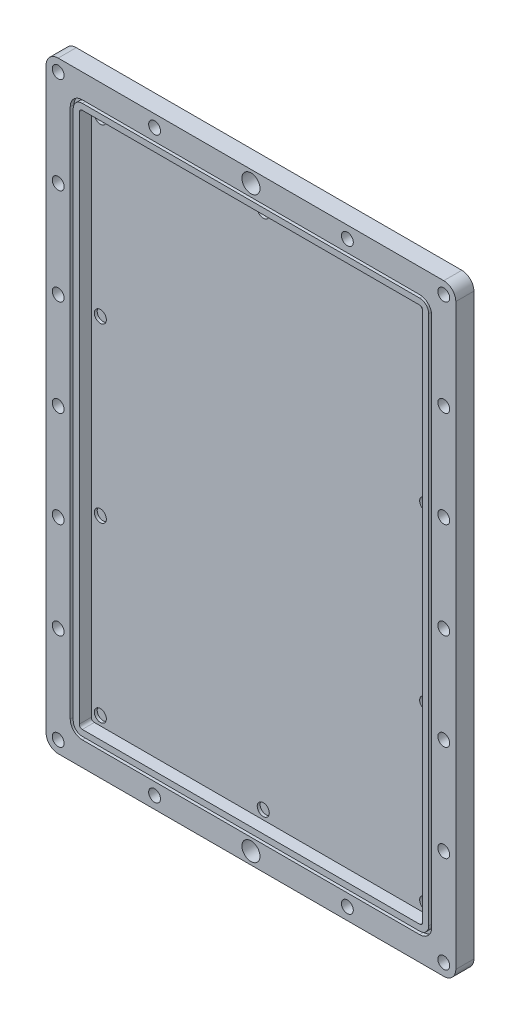
SolidWorks part; units mm, degrees
ref_plane "Front Plane" through (0, 0, 0) normal (0, 0, 1) x (1, 0, 0)
ref_plane "Top Plane" through (0, 0, 0) normal (0, 1, 0) x (1, 0, 0)
ref_plane "Right Plane" through (0, 0, 0) normal (1, 0, 0) x (0, 0, -1)
sketch "Sketch1" plane through (0, 0, 0) normal (0, 0, 1) x (1, 0, 0)
  line L1 (0, 0) -> (215.9, 0)
  line L2 (0, 0) -> (0, 317.5)
  line L3 (0, 317.5) -> (215.9, 317.5)
  line L4 (215.9, 0) -> (215.9, 317.5)
  dimension "D1" = 317.5
  dimension "D2" = 215.9
extrude "Boss-Extrude1" add sketch "Sketch1" along normal blind 9.525
sketch "Sketch4" plane through (0, 0, 9.525) normal (0, 0, 1) x (1, 0, 0)
  line L3 (0, 317.5) -> (0, 0) construction
  line L4 (6.35, 311.15) -> (209.55, 311.15) construction
  line L5 (6.35, 311.15) -> (6.35, 6.35) construction
  line L6 (6.35, 6.35) -> (209.55, 6.35) construction
  line L7 (209.55, 311.15) -> (209.55, 6.35) construction
  line L8 (215.9, 317.5) -> (0, 317.5) construction
  line L9 (215.9, 0) -> (215.9, 317.5) construction
  line L10 (0, 0) -> (215.9, 0) construction
  circle A0 centre (6.35, 6.35) radius 3.1242
  circle A1 centre (6.35, 311.15) radius 3.1242
  circle A2 centre (209.55, 311.15) radius 3.1242
  circle A3 centre (209.55, 6.35) radius 3.1242
  circle A4 centre (57.15, 311.15) radius 3.1242
  circle A5 centre (57.15, 6.35) radius 3.1242
  circle A6 centre (107.95, 311.15) radius 3.1242
  circle A7 centre (107.95, 6.35) radius 3.1242
  circle A8 centre (158.75, 311.15) radius 3.1242
  circle A9 centre (158.75, 6.35) radius 3.1242
  circle A10 centre (6.35, 260.35) radius 3.1242
  circle A11 centre (209.55, 260.35) radius 3.1242
  circle A12 centre (6.35, 209.55) radius 3.1242
  circle A13 centre (209.55, 209.55) radius 3.1242
  circle A14 centre (6.35, 158.75) radius 3.1242
  circle A15 centre (209.55, 158.75) radius 3.1242
  circle A16 centre (6.35, 107.95) radius 3.1242
  circle A17 centre (209.55, 107.95) radius 3.1242
  circle A18 centre (6.35, 57.15) radius 3.1242
  circle A19 centre (209.55, 57.15) radius 3.1242
  dimension "D5" = 6.2484
  dimension "D1" = 6.35
  dimension "D2" = 6.35
  dimension "D3" = 6.35
  dimension "D4" = 6.35
  dimension "D6" = 4
  dimension "D7" = 6
extrude "Cut-Extrude1" cut sketch "Sketch4" against normal through all
sketch "Sketch5" plane through (0, 0, 9.525) normal (0, 0, 1) x (1, 0, 0)
  line L0 (0, 317.5) -> (0, 0) construction
  line L1 (19.05, 304.8) -> (196.85, 304.8)
  line L2 (12.7, 298.45) -> (12.7, 19.05)
  line L3 (19.05, 12.7) -> (196.85, 12.7)
  line L4 (203.2, 298.45) -> (203.2, 19.05)
  line L5 (215.9, 317.5) -> (0, 317.5) construction
  line L6 (215.9, 0) -> (215.9, 317.5) construction
  line L7 (0, 0) -> (215.9, 0) construction
  line L8 (19.05, 14.2875) -> (196.85, 14.2875)
  line L9 (14.2875, 298.45) -> (14.2875, 19.05)
  line L10 (19.05, 303.2125) -> (196.85, 303.2125)
  line L11 (201.6125, 298.45) -> (201.6125, 19.05)
  arc A0 (196.85, 12.7) -> (203.2, 19.05) centre (196.85, 19.05) ccw
  arc A1 (12.7, 19.05) -> (19.05, 12.7) centre (19.05, 19.05) ccw
  arc A2 (196.85, 304.8) -> (203.2, 298.45) centre (196.85, 298.45) cw
  arc A3 (19.05, 304.8) -> (12.7, 298.45) centre (19.05, 298.45) ccw
  arc A4 (14.2875, 19.05) -> (19.05, 14.2875) centre (19.05, 19.05) ccw
  arc A5 (19.05, 303.2125) -> (14.2875, 298.45) centre (19.05, 298.45) ccw
  arc A6 (196.85, 303.2125) -> (201.6125, 298.45) centre (196.85, 298.45) cw
  arc A7 (196.85, 14.2875) -> (201.6125, 19.05) centre (196.85, 19.05) ccw
  dimension "D5" = 6.35
  dimension "D1" = 12.7
  dimension "D2" = 12.7
  dimension "D3" = 12.7
  dimension "D4" = 12.7
  dimension "D6" = 1.5875
  dimension "D7" = 1.5875
extrude "Cut-Extrude2" cut sketch "Sketch5" against normal blind 2.032 contours L1 A3 L2 A1 L3 A0 L4 A2 A7 L8 A4 L9 A5 L10 A6 L11 region at (107.95, 304.4513, 9.525)
sketch "Sketch6" plane through (0, 0, 9.525) normal (0, 0, 1) x (1, 0, 0)
  line L8 (198.4375, 19.05) -> (198.4375, 298.45)
  line L9 (196.85, 300.0375) -> (19.05, 300.0375)
  line L10 (17.4625, 298.45) -> (17.4625, 19.05)
  line L11 (19.05, 17.4625) -> (196.85, 17.4625)
  line L12 (198.4375, 19.05) -> (198.4375, 298.45)
  line L13 (196.85, 300.0375) -> (19.05, 300.0375)
  line L14 (17.4625, 298.45) -> (17.4625, 19.05)
  line L15 (19.05, 17.4625) -> (196.85, 17.4625)
  arc A8 (196.85, 17.4625) -> (198.4375, 19.05) centre (196.85, 19.05) ccw
  arc A9 (198.4375, 298.45) -> (196.85, 300.0375) centre (196.85, 298.45) ccw
  arc A10 (19.05, 300.0375) -> (17.4625, 298.45) centre (19.05, 298.45) ccw
  arc A11 (17.4625, 19.05) -> (19.05, 17.4625) centre (19.05, 19.05) ccw
  arc A12 (196.85, 17.4625) -> (198.4375, 19.05) centre (196.85, 19.05) ccw
  arc A13 (198.4375, 298.45) -> (196.85, 300.0375) centre (196.85, 298.45) ccw
  arc A14 (19.05, 300.0375) -> (17.4625, 298.45) centre (19.05, 298.45) ccw
  arc A15 (17.4625, 19.05) -> (19.05, 17.4625) centre (19.05, 19.05) ccw
  dimension "D1" = 3.175
extrude "Cut-Extrude3" cut sketch "Sketch6" against normal blind 6.35
sketch "Sketch7" plane through (0, 0, 3.175) normal (0, 0, 1) x (1, 0, 0)
  line L0 (196.85, 300.0375) -> (19.05, 300.0375) construction
  line L1 (22.225, 295.275) -> (193.675, 295.275) construction
  line L2 (22.225, 295.275) -> (22.225, 22.225) construction
  line L3 (22.225, 22.225) -> (193.675, 22.225) construction
  line L4 (193.675, 295.275) -> (193.675, 22.225) construction
  line L5 (17.4625, 298.45) -> (17.4625, 19.05) construction
  line L6 (198.4375, 19.05) -> (198.4375, 298.45) construction
  line L7 (19.05, 17.4625) -> (196.85, 17.4625) construction
  circle A0 centre (22.225, 295.275) radius 3.175
  circle A1 centre (193.675, 295.275) radius 3.175
  circle A2 centre (22.225, 22.225) radius 3.175
  circle A3 centre (193.675, 22.225) radius 3.175
  circle A4 centre (108.077, 22.225) radius 3.175
  circle A5 centre (108.077, 295.275) radius 3.175
  circle A6 centre (22.225, 204.343) radius 3.175
  circle A7 centre (193.675, 204.343) radius 3.175
  circle A8 centre (22.225, 113.411) radius 3.175
  circle A9 centre (193.675, 113.411) radius 3.175
  dimension "D5" = 6.35
  dimension "D1" = 4.7625
  dimension "D2" = 4.7625
  dimension "D3" = 4.7625
  dimension "D4" = 4.7625
  dimension "D6" = 2
  dimension "D7" = 3
extrude "Cut-Extrude4" cut sketch "Sketch7" against normal blind 1.524
sketch "Sketch8" plane through (0, 0, 9.525) normal (0, 0, 1) x (1, 0, 0)
  circle A0 centre (107.95, 311.15) radius 4.7625
  circle A1 centre (107.95, 6.35) radius 4.7625
  dimension "D1" = 9.525
extrude "Cut-Extrude5" cut sketch "Sketch8" against normal through all
fillet "Fillet1" radius 6.35 4 edges at (215.9, 0, 4.7625) (0, 0, 4.7625) (215.9, 317.5, 4.7625) (0, 317.5, 4.7625)
